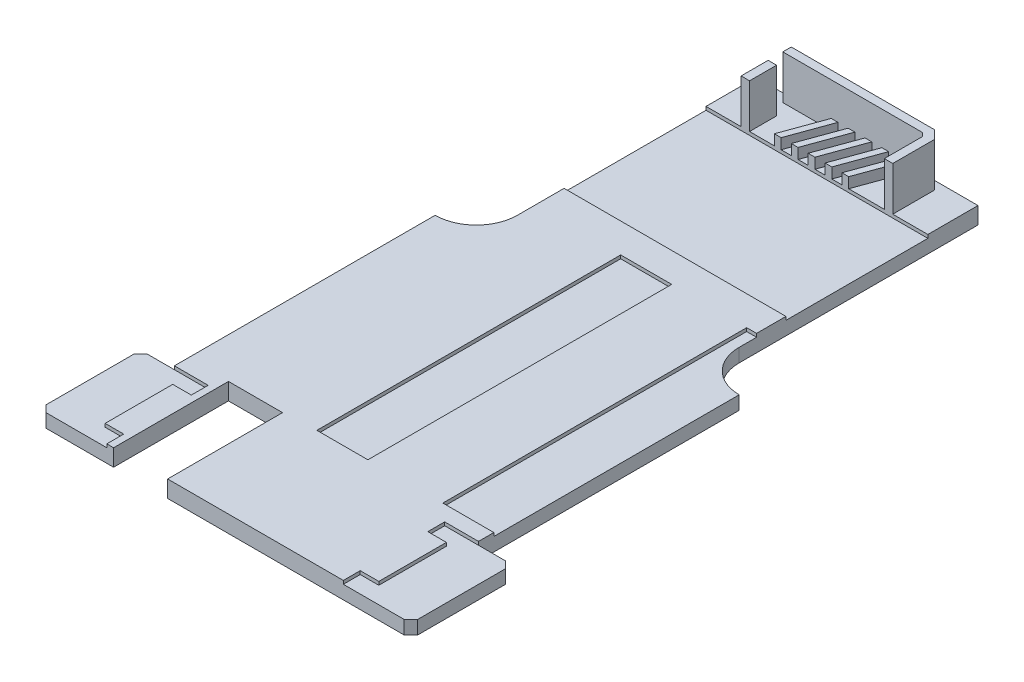
SolidWorks part; units mm, degrees
ref_plane "Front Plane" through (0, 0, 0) normal (0, 0, 1) x (1, 0, 0)
ref_plane "Top Plane" through (0, 0, 0) normal (0, 1, 0) x (1, 0, 0)
ref_plane "Right Plane" through (0, 0, 0) normal (1, 0, 0) x (0, 0, -1)
sketch "Sketch1" plane through (0, 0, 0) normal (0, 1, 0) x (1, 0, 0)
  line L1 (-45, 95) -> (45, 95)
  line L2 (-45, 95) -> (-45, -95)
  line L3 (-45, -95) -> (45, -95)
  line L4 (45, 95) -> (45, -95)
  line L5 (-45, 95) -> (45, -95) construction
  line L6 (-45, -95) -> (45, 95) construction
  point P0 (0, 0)
  dimension "D1" = 190
  dimension "D2" = 90
extrude "Boss-Extrude1" add sketch "Sketch1" along normal blind 5 contours L2 L1 L4 L3
sketch "Sketch2" plane through (0, 0, 0) normal (0, 1, 0) x (1, 0, 0)
  line L0 (-45, 95) -> (-45, -95) construction
  line L1 (-45, -65) -> (-55, -65)
  line L2 (-45, -65) -> (-45, -95)
  line L3 (-45, -95) -> (-55, -95)
  line L4 (-55, -65) -> (-55, -95)
  line L5 (45, 95) -> (45, -95) construction
  line L6 (45, -65) -> (55, -65)
  line L7 (45, -65) -> (45, -95)
  line L8 (45, -95) -> (55, -95)
  line L9 (55, -65) -> (55, -95)
  line L10 (-45, -95) -> (45, -95) construction
  dimension "D1" = 30
  dimension "D2" = 10
extrude "Boss-Extrude2" add sketch "Sketch2" along normal blind 5
chamfer "Chamfer1" distance 2 angle 45 4 edges at (55, 2.5, 95) (55, 2.5, 65) (-55, 2.5, 95) (-55, 2.5, 65)
sketch "Sketch3" plane through (0, 5, 0) normal (0, 1, 0) x (1, 0, 0)
  line L0 (-53, -95) -> (53, -95) construction
  line L1 (-33, -95) -> (-17, -95)
  line L2 (-33, -95) -> (-33, -61)
  line L3 (-33, -61) -> (-17, -61)
  line L4 (-17, -95) -> (-17, -61)
  line L5 (-55, -67) -> (-55, -93) construction
  dimension "D1" = 22
  dimension "D2" = 16
  dimension "D3" = 34
extrude "Cut-Extrude1" cut sketch "Sketch3" against normal blind 50 contours L2 L1 L4 L3
sketch "Sketch4" plane through (0, 5, 0) normal (0, 1, 0) x (1, 0, 0)
  line L0 (-45, 80.1598) -> (-45, 38.1598)
  line L1 (-45, 95) -> (-45, -65) construction
  line L2 (-48, 80.1598) -> (48, 80.1598) construction
  line L4 (-45, 38.1598) -> (45, 38.1598)
  line L5 (45, 95) -> (45, -65) construction
  line L6 (45, 38.1598) -> (45, 80.1598)
  line L7 (45, 80.1598) -> (-45, 80.1598)
  dimension "D1" = 42
extrude "Cut-Extrude2" cut sketch "Sketch4" against normal blind 1
sketch "Sketch7" plane through (0, 5, 0) normal (0, 1, 0) x (1, 0, 0)
  line L0 (-7.3823, 29.4629) -> (-7.3823, -60.4534)
  line L1 (-7.3823, -60.4534) -> (7.7177, -60.4534)
  line L2 (7.7177, -60.4534) -> (7.7177, 29.4629)
  line L3 (7.7177, 29.4629) -> (-7.3823, 29.4629)
  line L4 (29.9, 29.4629) -> (29.9, -60.4534)
  line L5 (29.9, -60.4534) -> (45, -60.4534)
  line L6 (45, 38.1598) -> (45, -65) construction
  line L7 (45, -60.4534) -> (45, 29.4629)
  line L8 (45, 29.4629) -> (29.9, 29.4629)
  line M17 (45, -65) -> (45, 38.1598)
  dimension "D1" = 15.1
  dimension "D2" = 15.1
extrude "Cut-Extrude7" cut sketch "Sketch7" against normal blind 1 contours L8 L4 L5 M17 | L3 L0 L1 L2 region at (37.45, 5, 15.4953)
sketch "Sketch14" plane through (0, 0, 0) normal (0, 1, 0) x (1, 0, 0)
  line L0 (-45, 47.2671) -> (-34.685, 30.799)
  line L1 (-45, 80.1598) -> (-45, 38.1598) construction
  line L2 (-45, 38.1598) -> (-45, -65) construction
  line L3 (-45, 47.2671) -> (-45, 12.1668)
  line L4 (0, -6.2305) -> (0, 15.6399) construction
  line L5 (45, 47.2671) -> (45, 12.1668)
  line L6 (45, 47.2671) -> (34.685, 30.799)
  arc A0 (-34.685, 30.799) -> (-45, 12.1668) centre (-45, 24.3381) cw
  arc A1 (34.685, 30.799) -> (45, 12.1668) centre (45, 24.3381) ccw
extrude "Cut-Extrude9" cut sketch "Sketch14" along normal through all both and the other way through all
sketch "Sketch15" plane through (0, 0, 0) normal (0, 1, 0) x (1, 0, 0)
  line L0 (-34.685, 30.799) -> (-39.2956, 38.1598) construction
  line L2 (-34.685, 30.799) -> (-39.2956, 38.1598)
  line L5 (-32.9901, 31.8607) -> (-36.9356, 38.1598)
  line L9 (-45, 12.1668) -> (-45, 10.1668)
  line L10 (0, 0) -> (0, 12.1668)
  line L11 (45, 12.1668) -> (45, 10.1668)
  line L12 (34.685, 30.799) -> (39.2956, 38.1598)
  line L17 (32.9901, 31.8607) -> (36.9356, 38.1598)
  line L18 (-39.2956, 38.1598) -> (-36.9356, 38.1598)
  line L19 (-39.2956, 38.1598) -> (39.2956, 38.1598) construction
  line L20 (-32.9901, 31.8607) -> (-37.6006, 39.2215) construction
  line L21 (-45, 47.2671) -> (-39.2956, 38.1598) construction
  line L22 (-43.305, 48.3288) -> (-37.6006, 39.2215) construction
  line L23 (39.2956, 38.1598) -> (36.9356, 38.1598)
  arc A0 (-45, 12.1668) -> (-34.685, 30.799) centre (-45, 24.3381) ccw construction
  arc A1 (-45, 12.1668) -> (-34.685, 30.799) centre (-45, 24.3381) ccw
  arc A2 (-45, 10.1668) -> (-32.9901, 31.8607) centre (-45, 24.3381) ccw
  arc A3 (45, 12.1668) -> (34.685, 30.799) centre (45, 24.3381) cw
  arc A4 (45, 10.1668) -> (32.9901, 31.8607) centre (45, 24.3381) cw
  dimension "D1" = 2
extrude "Boss-Extrude3" [suppressed] add sketch "Sketch15" along normal blind 2 from surface contours A1 L2 L18 L5 A2 L9 | A3 L12 L23 L17 A4 L11
sketch "Sketch16" plane through (0, 0, 0) normal (0, 1, 0) x (1, 0, 0)
  line L0 (-32.8287, 95) -> (-32.8287, 24.3381)
  line L1 (-45, 95) -> (45, 95) construction
  line L4 (-34.685, 30.799) -> (-45, 47.2671)
  line L5 (-45, 47.2671) -> (-45, 95)
  line L6 (-45, 95) -> (-32.8287, 95)
  line L7 (0, 0) -> (0, 50000) construction
  line L13 (45, 95) -> (32.8287, 95)
  line L14 (45, 47.2671) -> (45, 95)
  line L15 (34.685, 30.799) -> (45, 47.2671)
  line L16 (32.8287, 95) -> (32.8287, 24.3381)
  arc A0 (-45, 12.1668) -> (-34.685, 30.799) centre (-45, 24.3381) ccw construction
  arc A1 (-32.8287, 24.3381) -> (-34.685, 30.799) centre (-45, 24.3381) ccw
  arc A2 (32.8287, 24.3381) -> (34.685, 30.799) centre (45, 24.3381) cw
extrude "Cut-Extrude10" cut sketch "Sketch16" along normal through all both and the other way through all
sketch "Sketch17" plane through (0, 0, 0) normal (0, 1, 0) x (1, 0, 0)
  line L0 (-19.94, 80.1598) -> (-19.94, 88.1598)
  line L1 (32.8287, 80.1598) -> (-32.8287, 80.1598) construction
  line L2 (-19.94, 69.0848) -> (-19.94, 88.4854) construction
  line L4 (-22.44, 92.4998) -> (18.94, 92.4998)
  line L5 (18.94, 92.4998) -> (19.94, 91.4998)
  line L7 (19.94, 91.4998) -> (18.94, 92.4998) construction
  line L10 (19.94, 91.4998) -> (19.94, 80.1598)
  line L11 (19.94, 69.0848) -> (19.94, 88.4854) construction
  line L12 (-22.44, 80.1598) -> (-22.44, 88.1598)
  line L14 (-22.44, 94.9998) -> (19.9756, 94.9998)
  line L15 (19.9756, 94.9998) -> (22.44, 92.5354)
  line L16 (22.44, 92.5354) -> (22.44, 80.1598)
  line L17 (-22.44, 80.1598) -> (-19.94, 80.1598)
  line L18 (19.94, 80.1598) -> (22.44, 80.1598)
  line L19 (-22.44, 88.1598) -> (-19.94, 88.1598)
  line L20 (-22.44, 92.4998) -> (-22.44, 94.9998)
  line L21 (-22.44, 80.1598) -> (-22.44, 92.5354) construction
  line L22 (-19.94, 80.1598) -> (-19.94, 91.4998) construction
  line L23 (-19.94, 91.4998) -> (-18.94, 92.4998) construction
  line L24 (-18.94, 92.4998) -> (18.94, 92.4998) construction
  line L25 (-19.9756, 94.9998) -> (19.9756, 94.9998) construction
  line L26 (-22.44, 92.5354) -> (-19.9756, 94.9998) construction
  dimension "D2" = 8
  dimension "D1" = 2.5
extrude "Boss-Extrude4" add sketch "Sketch17" along normal blind 13 from surface starting at face at (0, 5, -87.5799)
sketch "Sketch18" plane through (0, 5, 0) normal (0, 1, 0) x (1, 0, 0)
  line L6 (-12.5996, 80.1598) -> (-10.5996, 80.1598)
  line L7 (19.94, 80.1598) -> (-19.94, 80.1598) construction
  line L8 (-10.5996, 80.1598) -> (-6.1082, 92.4998)
  line L9 (-22.44, 92.4998) -> (18.94, 92.4998) construction
  line L10 (-6.1082, 92.4998) -> (-8.1082, 92.4998)
  line L11 (-8.1082, 92.4998) -> (-12.5996, 80.1598)
  line L12 (-3.1082, 92.4998) -> (-7.5996, 80.1598)
  line L13 (-7.5996, 80.1598) -> (-5.5996, 80.1598)
  line L14 (-5.5996, 80.1598) -> (-1.1082, 92.4998)
  line L15 (-1.1082, 92.4998) -> (-3.1082, 92.4998)
  line L16 (1.8918, 92.4998) -> (-2.5996, 80.1598)
  line L17 (-2.5996, 80.1598) -> (-0.5996, 80.1598)
  line L18 (-0.5996, 80.1598) -> (3.8918, 92.4998)
  line L19 (3.8918, 92.4998) -> (1.8918, 92.4998)
  line L20 (6.8918, 92.4998) -> (2.4004, 80.1598)
  line L21 (2.4004, 80.1598) -> (4.4004, 80.1598)
  line L22 (4.4004, 80.1598) -> (8.8918, 92.4998)
  line L23 (8.8918, 92.4998) -> (6.8918, 92.4998)
  line L24 (11.8918, 92.4998) -> (7.4004, 80.1598)
  line L25 (7.4004, 80.1598) -> (9.4004, 80.1598)
  line L26 (9.4004, 80.1598) -> (13.8918, 92.4998)
  line L27 (13.8918, 92.4998) -> (11.8918, 92.4998)
  dimension "D1" = 2
  dimension "D2" = 70
  dimension "D3" = 5
extrude "Boss-Extrude5" add sketch "Sketch18" along normal blind 3.1
sketch "Sketch19" plane through (0, 0, 0) normal (0, 1, 0) x (1, 0, 0)
  line L0 (-35, -65) -> (-35, -70)
  line L1 (-35, -70) -> (-40.5, -70)
  line L2 (-40.5, -70) -> (-40.5, -90)
  line L3 (-40.5, -90) -> (-35, -90)
  line L4 (-35, -90) -> (-35, -95)
  line L5 (-53, -95) -> (-33, -95) construction
  line L6 (-35, -95) -> (-53, -95)
  line L7 (-53, -95) -> (-55, -93)
  line L8 (-55, -93) -> (-55, -67)
  line L9 (-55, -67) -> (-53, -65)
  line L10 (-53, -65) -> (-35, -65)
  point P12 (-40.5, -70)
extrude "Cut-Extrude11" cut sketch "Sketch19" against normal blind 1 from surface starting at face at (0.1677, 5, 15.4953)
mirror "Mirror1" about plane through (0, 0, 0) normal (1, 0, 0) of "Cut-Extrude11"
